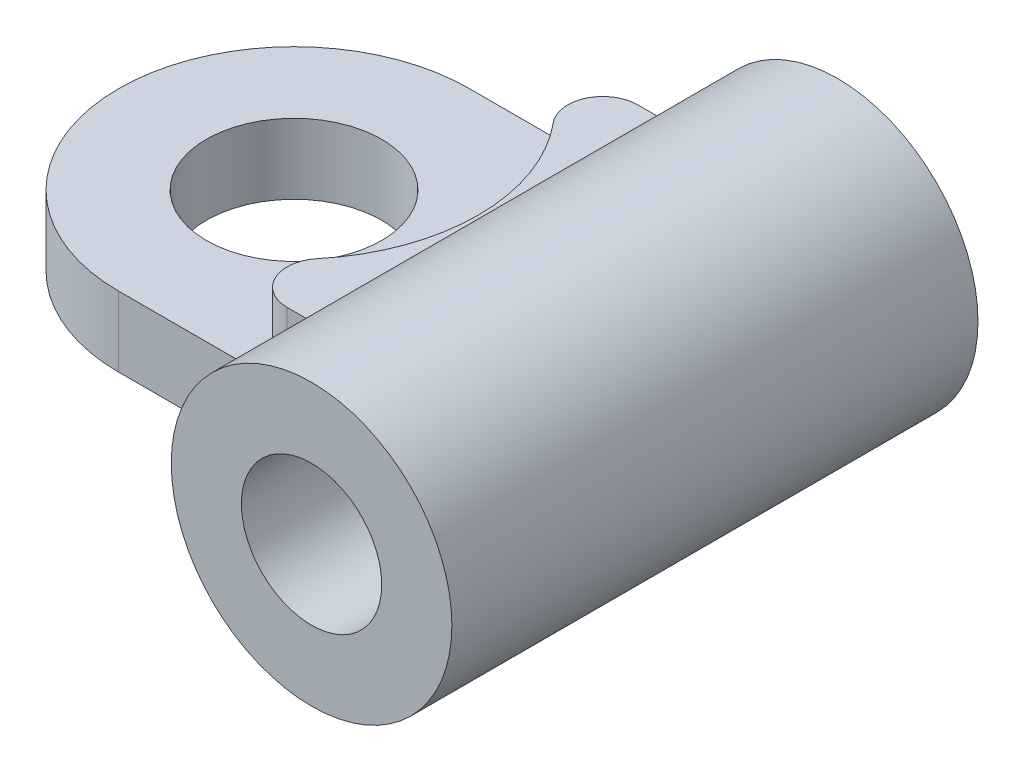
SolidWorks part; units mm, degrees
ref_plane "Спереди" through (0, 0, 0) normal (0, 0, 1) x (1, 0, 0)
ref_plane "Сверху" through (0, 0, 0) normal (0, 1, 0) x (1, 0, 0)
ref_plane "Справа" through (0, 0, 0) normal (1, 0, 0) x (0, 0, -1)
sketch "Sketch1" plane through (0, 0, 0) normal (0, 0, 1) x (1, 0, 0)
  circle A0 centre (0, 0) radius 4
  circle A1 centre (0, 0) radius 8
  dimension "D1" = 8
  dimension "D2" = 4
extrude "Boss-Extrude1" add sketch "Sketch1" along normal blind 30
sketch "Sketch2" plane through (0, 0, 0) normal (0, 1, 0) x (1, 0, 0)
  line L1 (-18, -3) -> (-5, -3)
  line L2 (-18, -23) -> (-5, -23)
  line L3 (-5, -23) -> (-5, -3)
  line L4 (8, 0) -> (-8, 0) construction
  line L5 (-8, 0) -> (-8, -30) construction
  circle A0 centre (-18, -13) radius 10
  point P10 (0, 0)
  dimension "D1" = 20
  dimension "D2" = 3
  dimension "D3" = 3
extrude "Boss-Extrude2" add sketch "Sketch2" along normal mid plane 8 separate body contours A0 | A0 L3 L1 | A0 L2 L3 region at (-11.5, 0, 3.2385) region at (-18, 0, 13)
sketch "Sketch3" plane through (0, 4, 0) normal (0, 1, 0) x (1, 0, 0)
  circle A0 centre (-18, -13) radius 10.5
  dimension "D1" = 21
extrude "Cut-Extrude1" cut sketch "Sketch3" against normal blind 4
fillet "Fillet1" radius 2 2 edges at (-14.7984, 2, 23) (-14.7984, 2, 3)
sketch "Sketch4" plane through (0, 0, 0) normal (0, 1, 0) x (1, 0, 0)
  circle A0 centre (-18, -13) radius 5
  dimension "D1" = 10
extrude "Cut-Extrude2" cut sketch "Sketch4" against normal blind 4
